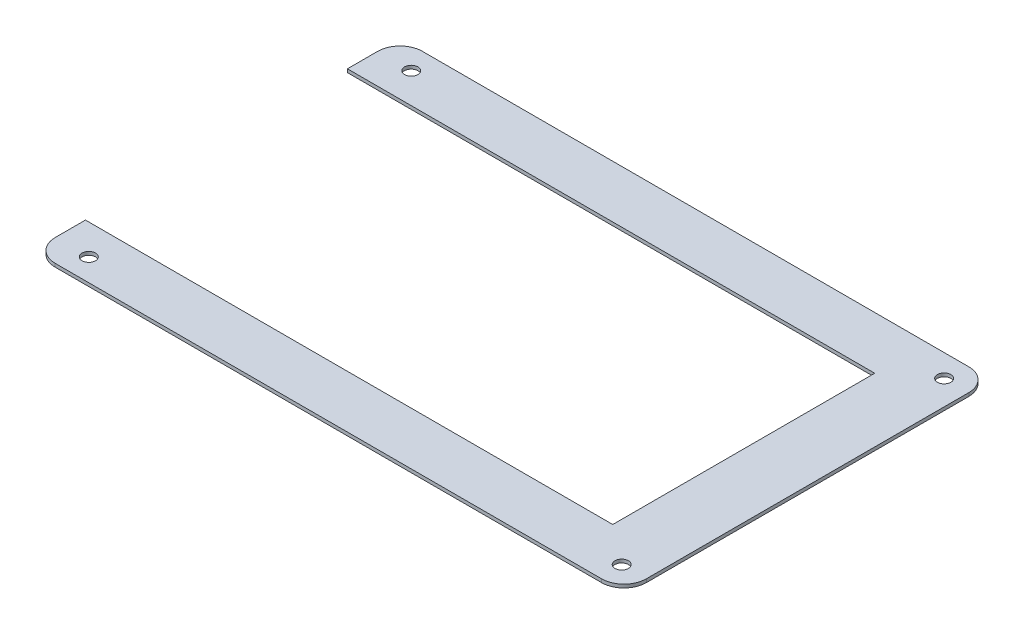
SolidWorks part; units mm, degrees
ref_plane "Front Plane" through (0, 0, 0) normal (0, 0, 1) x (1, 0, 0)
ref_plane "Top Plane" through (0, 0, 0) normal (0, 1, 0) x (1, 0, 0)
ref_plane "Right Plane" through (0, 0, 0) normal (1, 0, 0) x (0, 0, -1)
sketch "Sketch1" plane through (0, 0, 0) normal (0, 1, 0) x (1, 0, 0)
  line L0 (-127.2073, 58.5) -> (-127.2073, 72)
  line L1 (-117.2073, -82) -> (126.7927, -82)
  line L2 (-127.2073, -72) -> (-127.2073, -58.5)
  line L3 (-117.2073, 82) -> (126.7927, 82)
  line L4 (136.7927, -72) -> (136.7927, 72)
  line L7 (-127.2073, 58.5) -> (108.2927, 58.5)
  line L9 (-127.2073, -58.5) -> (108.2927, -58.5)
  line L10 (108.2927, 58.5) -> (108.2927, -58.5)
  arc A0 (-117.2073, -82) -> (-127.2073, -72) centre (-117.2073, -72) cw
  arc A1 (126.7927, -82) -> (136.7927, -72) centre (126.7927, -72) ccw
  arc A2 (136.7927, 72) -> (126.7927, 82) centre (126.7927, 72) ccw
  arc A3 (-117.2073, 82) -> (-127.2073, 72) centre (-117.2073, 72) ccw
  circle A4 centre (125.7927, 72) radius 3
  circle A5 centre (-112.2073, 72) radius 3
  circle A6 centre (-112.2073, -72) radius 3
  circle A7 centre (125.7927, -72) radius 3
  point P0 (0, 0)
  point P2 (108.2927, 0)
  point P27 (0, 0)
  point P28 (0, 0)
  point P29 (0, 0)
  point P30 (0, 0)
  dimension "D3" = 10
  dimension "D6" = 6
  dimension "D7" = 238
  dimension "D8" = 144
  dimension "D9" = 10
  dimension "D10" = 11
  dimension "D1" = 164
  dimension "D2" = 264
  dimension "D4" = 28.5
  dimension "D5" = 23.5
base flange "Base-Flange1" sketch "Sketch1" thickness 1.5 reverse thickness direction yes parameters "D1"=2
sketch "Bend-Lines1" [suppressed] plane through (0, 0, 0) normal (0, 1, 0) x (1, 0, 0)
sketch "Bounding-Box1" [suppressed] plane through (0, 0, 0) normal (0, 1, 0) x (1, 0, 0)
sheet metal parameters "Sheet-Metal1" thickness 1.5 parameters "D1"=2
flat pattern "Flat-Pattern1" [suppressed]
sketch "Bend-Lines2" plane through (0, 0, 0) normal (0, 1, 0) x (1, 0, 0)
sketch3d "Bounding-Box2" [suppressed]
  line L0 (-10, 154, 0) -> (254, 154, 0) construction
  line L1 (-10, -10, 0) -> (254, -10, 0) construction
  line L2 (-10, 154, 0) -> (-10, -10, 0) construction
  line L3 (254, 154, 0) -> (254, -10, 0) construction
